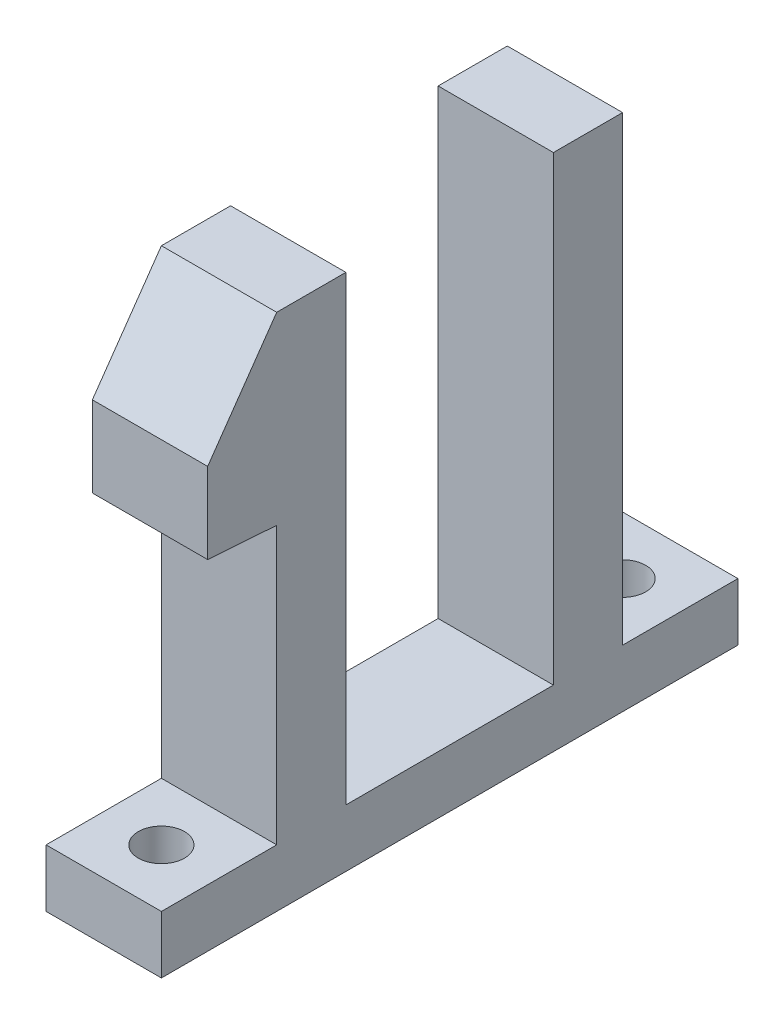
SolidWorks part; units mm, degrees
ref_plane "前视基准面" through (0, 0, 0) normal (0, 0, 1) x (1, 0, 0)
ref_plane "上视基准面" through (0, 0, 0) normal (0, 1, 0) x (1, 0, 0)
ref_plane "右视基准面" through (0, 0, 0) normal (1, 0, 0) x (0, 0, -1)
other "Configuration Table"
sketch "草图1" plane through (0, 0, 0) normal (0, 1, 0) x (1, 0, 0)
  line L0 (0, 0) -> (-5.8775, 0) construction
  line L1 (-2.5, 12.5) -> (2.5, 12.5)
  line L2 (-2.5, 12.5) -> (-2.5, -12.5)
  line L3 (-2.5, -12.5) -> (2.5, -12.5)
  line L4 (2.5, 12.5) -> (2.5, -12.5)
  line L5 (-2.5, 12.5) -> (2.5, -12.5) construction
  line L6 (-2.5, -12.5) -> (2.5, 12.5) construction
  circle A0 centre (0, 10) radius 1
  circle A1 centre (0, -10) radius 1
  point P0 (0, 0)
  dimension "D4" = 2
  dimension "D1" = 25
  dimension "D2" = 5
  dimension "D3" = 10
extrude "凸台-拉伸1" add sketch "草图1" along normal blind 2.5
sketch "草图3" plane through (0, 2.5, 0) normal (0, 1, 0) x (1, 0, 0)
  line L1 (-2.5, 7.5) -> (2.5, 7.5)
  line L2 (-2.5, 7.5) -> (-2.5, -7.5)
  line L3 (-2.5, -7.5) -> (2.5, -7.5)
  line L4 (2.5, 7.5) -> (2.5, -7.5)
  line L5 (-2.5, 7.5) -> (2.5, -7.5) construction
  line L6 (-2.5, -7.5) -> (2.5, 7.5) construction
  point P0 (0, 0)
  dimension "D1" = 15
  dimension "D2" = 5
extrude "凸台-拉伸2" add sketch "草图3" along normal blind 20
sketch "草图5" plane through (2.5, 0, 0) normal (1, 0, 0) x (0, 0, -1)
  line L0 (-7.5, 14.5) -> (-10.4927, 14.7093)
  line L1 (-7.5, 22.5) -> (-7.5, 2.5) construction
  line L2 (-2.651, 14.5) -> (-11.4829, 14.5) construction
  line L4 (-10.4927, 14.7093) -> (-10.4927, 18.2093)
  line L5 (-10.4927, 18.2093) -> (-7.5, 22.5)
  line L6 (-7.5, 22.5) -> (-7.5, 14.5)
  dimension "D1" = 3
  dimension "D2" = 3.5
sketch "草图6" plane through (2.5, 0, 0) normal (1, 0, 0) x (0, 0, -1)
  line L0 (-7.5, 22.5) -> (7.5, 22.5) construction
  line L1 (-4.5, 22.5) -> (4.5, 22.5)
  line L2 (-4.5, 22.5) -> (-4.5, 2.5)
  line L3 (-4.5, 2.5) -> (4.5, 2.5)
  line L4 (4.5, 22.5) -> (4.5, 2.5)
  line L5 (-16.1796, 2.5) -> (10.5553, 2.5) construction
  line L6 (-7.5, 22.5) -> (-7.5, 2.5) construction
  line L7 (7.5, 22.5) -> (7.5, 2.5) construction
  dimension "D1" = 3
  dimension "D2" = 3
extrude "切除-拉伸1" cut sketch "草图6" against normal through all
extrude "凸台-拉伸3" add sketch "草图5" against normal blind 5
